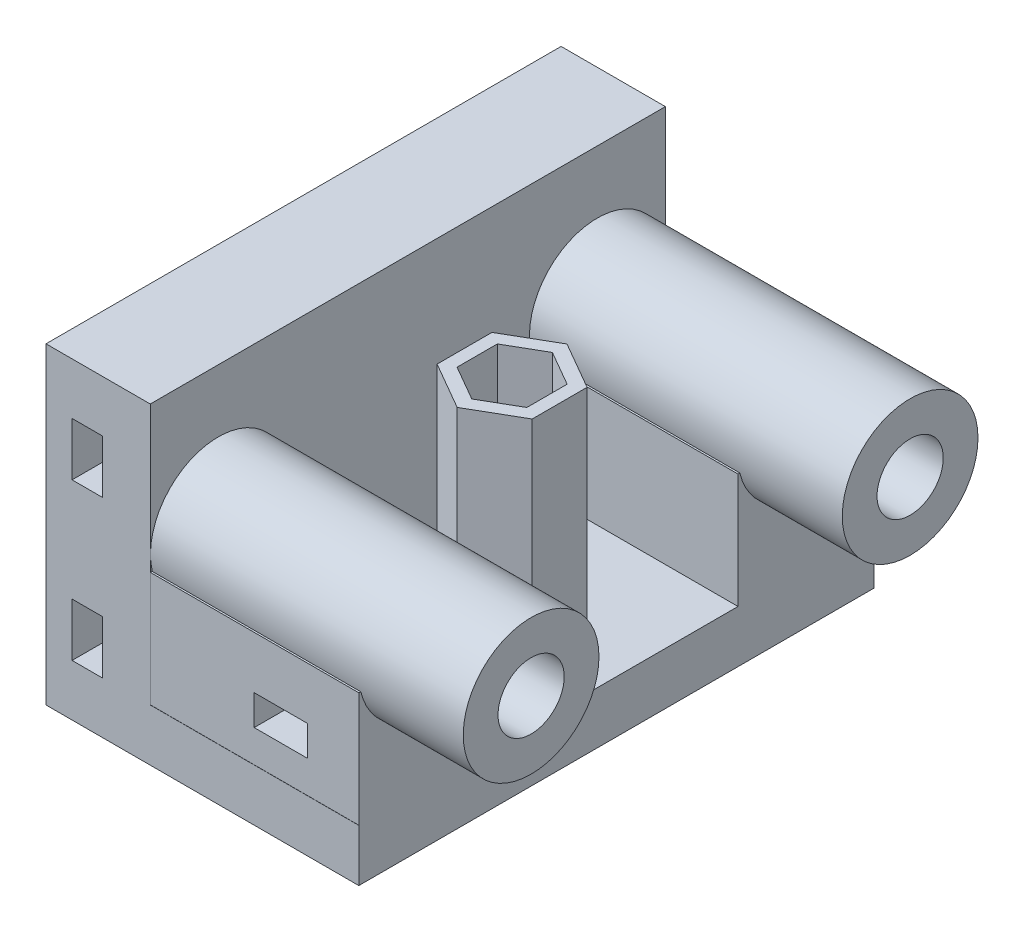
SolidWorks part; units mm, degrees
ref_plane "Front Plane" through (0, 0, 0) normal (0, 0, 1) x (1, 0, 0)
ref_plane "Top Plane" through (0, 0, 0) normal (0, 1, 0) x (1, 0, 0)
ref_plane "Right Plane" through (0, 0, 0) normal (1, 0, 0) x (0, 0, -1)
sketch "Sketch1" plane through (0, 0, 0) normal (1, 0, 0) x (0, 0, -1)
  line L1 (0, 0) -> (88.9, 0)
  line L2 (0, 0) -> (0, 76.2)
  line L3 (0, 76.2) -> (88.9, 76.2)
  line L4 (88.9, 0) -> (88.9, 76.2)
  dimension "D1" = 76.2
  dimension "D2" = 88.9
extrude "Boss-Extrude1" add sketch "Sketch1" along normal blind 25.4
sketch "Sketch2" plane through (0, 0, 0) normal (-1, 0, 0) x (0, 0, 1)
  line L0 (-88.9, 0) -> (-88.9, 76.2) construction
  line L1 (-82.55, 19.05) -> (-88.9, 19.05) construction
  line L2 (-82.55, 57.15) -> (-88.9, 57.15) construction
  line L3 (-44.45, 76.2) -> (-44.45, 0) construction
  line L4 (-88.9, 76.2) -> (0, 76.2) construction
  line L5 (0, 0) -> (-88.9, 0) construction
  circle A0 centre (-82.55, 57.15) radius 4.1021
  circle A1 centre (-82.55, 19.05) radius 4.1021
  circle A2 centre (-6.35, 19.05) radius 4.1021
  circle A3 centre (-6.35, 57.15) radius 4.1021
  dimension "D2" = 8.2042
  dimension "d1" = 19.05
  dimension "D3" = 6.35
  dimension "D4" = 38.1
  dimension "D5" = 76.2
extrude "Cut-Extrude1" cut sketch "Sketch2" against normal blind 19.05 contours A1 | A3 | A2 | A0 region at (0, 19.05, -82.55) region at (0, 19.05, -6.35) region at (0, 57.15, -6.35)
sketch "Sketch3" plane through (0, 0, 0) normal (0, 0, 1) x (1, 0, 0)
  line L0 (0, 61.2521) -> (0, 53.0479) construction
  line L1 (0, 57.15) -> (13.716, 57.15) construction
  line L2 (6.35, 63.627) -> (13.716, 63.627)
  line L3 (6.35, 63.627) -> (6.35, 50.673)
  line L4 (6.35, 50.673) -> (13.716, 50.673)
  line L5 (0, 38.1) -> (25.4, 38.1) construction
  line L6 (0, 76.2) -> (0, 0) construction
  line L7 (25.4, 76.2) -> (25.4, 0) construction
  line L8 (13.716, 12.573) -> (13.716, 25.527)
  line L9 (0, 61.2521) -> (0, 53.0479)
  line L11 (6.35, 25.527) -> (13.716, 25.527)
  line L12 (13.716, 63.627) -> (13.716, 50.673)
  line L13 (6.35, 12.573) -> (6.35, 25.527)
  line L14 (6.35, 12.573) -> (13.716, 12.573)
  dimension "D1" = 7.366
  dimension "D2" = 12.954
  dimension "D3" = 6.35
extrude "Cut-Extrude2" cut sketch "Sketch3" against normal blind 12.954 contours L12 L2 L3 L4 | L13 L14 L8 L11 region at (10.033, 57.15, 0) region at (10.033, 19.05, 0)
ref_plane "Plane1" through (0, 0, -44.45) normal (0, 0, 1) x (1, 0, 0)
mirror "Mirror1" about plane through (0, 0, -44.45) normal (0, 0, 1) of "Cut-Extrude2"
sketch "Sketch5" plane through (25.4, 0, 0) normal (1, 0, 0) x (0, 0, -1)
  line L0 (88.9, 0) -> (88.9, 76.2) construction
  line L1 (0, 0) -> (88.9, 0)
  line L2 (0, 0) -> (0, 12.7)
  line L3 (0, 12.7) -> (88.9, 12.7)
  line L4 (88.9, 0) -> (88.9, 12.7)
  dimension "D1" = 12.7
extrude "Boss-Extrude2" add sketch "Sketch5" along normal blind 50.8
sketch "Sketch6" plane through (25.4, 0, 0) normal (1, 0, 0) x (0, 0, -1)
  line L0 (-1.7145, 44.45) -> (90.6145, 44.45) construction
  line L3 (44.45, 76.2) -> (44.45, 12.7) construction
  line L4 (88.9, 76.2) -> (0, 76.2) construction
  line L5 (88.9, 12.7) -> (0, 12.7) construction
  line L6 (-1.7145, 44.45) -> (-1.7145, 60.9812) construction
  circle A0 centre (-1.7145, 44.45) radius 8.0645
  circle A1 centre (-1.7145, 44.45) radius 16.5312
  circle A2 centre (90.6145, 44.45) radius 8.0645
  circle A3 centre (90.6145, 44.45) radius 16.5312
  point P8 (44.45, 44.45)
  point P9 (44.45, 44.45)
  dimension "D2" = 16.129
  dimension "D3" = 8.4667
  dimension "D5" = 33.0623
  dimension "D4" = 16.5312
  dimension "V2" = 92.329
extrude "Boss-Extrude3" add sketch "Sketch6" along normal blind 76.2
sketch "Sketch7" plane through (0, 0, 0) normal (0, 0, 1) x (1, 0, 0)
  line L0 (25.4, 12.7) -> (25.4, 0)
  line L9 (25.4, 28.008) -> (25.4, 36.5699)
  line L10 (0, 76.2) -> (0, 0)
  line L11 (0, 0) -> (76.2, 0)
  line L12 (76.2, 0) -> (76.2, 12.7)
  line L13 (76.2, 12.7) -> (25.4, 12.7)
  line L14 (25.4, 12.7) -> (25.4, 28.008)
  line L15 (25.4, 28.008) -> (25.4, 36.5699)
  line L16 (25.4, 36.5699) -> (25.4, 52.3301)
  line L17 (25.4, 36.5699) -> (25.4, 52.3301)
  line L19 (25.4, 76.2) -> (0, 76.2)
  line L20 (0, 76.2) -> (0, 0)
  line L21 (0, 0) -> (76.2, 0)
  line L22 (76.2, 0) -> (76.2, 12.7)
  line L23 (76.2, 12.7) -> (25.4, 12.7)
  line L24 (25.4, 12.7) -> (25.4, 28.008)
  line L26 (25.4, 52.3301) -> (25.4, 60.892)
  line L27 (25.4, 52.3301) -> (25.4, 60.892)
  line L28 (25.4, 60.892) -> (25.4, 76.2)
  line L29 (25.4, 76.2) -> (0, 76.2)
  line L30 (25.4, 60.892) -> (25.4, 76.2)
  line M11 (13.716, 63.627) -> (13.716, 50.673)
  line M12 (13.716, 50.673) -> (6.35, 50.673)
  line M13 (6.35, 50.673) -> (6.35, 63.627)
  line M14 (6.35, 63.627) -> (13.716, 63.627)
  line M15 (0, 76.2) -> (0, 0)
  line M16 (0, 0) -> (76.2, 0)
  line M17 (76.2, 0) -> (76.2, 12.7)
  line M18 (76.2, 12.7) -> (25.4, 12.7)
  line M19 (25.4, 12.7) -> (25.4, 28.008)
  line M20 (25.4, 28.008) -> (25.4, 36.5699)
  line M21 (25.4, 36.5699) -> (25.4, 52.3301)
  line M22 (25.4, 52.3301) -> (25.4, 60.892)
  line M23 (25.4, 60.892) -> (25.4, 76.2)
  line M24 (25.4, 76.2) -> (0, 76.2)
  line M25 (6.35, 12.573) -> (6.35, 25.527)
  line M26 (6.35, 25.527) -> (13.716, 25.527)
  line M27 (13.716, 25.527) -> (13.716, 12.573)
  line M28 (13.716, 12.573) -> (6.35, 12.573)
  dimension "D1" = 0
extrude "Boss-Extrude4" add sketch "Sketch7" along normal blind 18.288 contours L0 M18 M16 M17 | L0 M19 M20 M21 M22 M23 M24 M15 M16 M28 M25 M26 M27 M14 M11 M12 M13 region at (50.8, 6.35, 0) region at (12.9917, 38.1, 0)
mirror "Mirror2" about plane through (0, 0, -44.45) normal (0, 0, 1) of "Boss-Extrude4"
sketch "Sketch8" plane through (0, 12.7, 0) normal (0, 1, 0) x (1, 0, 0)
  line L0 (101.6, 14.8167) -> (25.4, 14.8167) construction
  line L1 (25.4, -18.2457) -> (101.6, -18.2457) construction
  line L2 (101.6, 14.8167) -> (25.4, 14.8167)
  line L3 (25.4, -18.2457) -> (101.6, -18.2457)
  line L4 (25.4, 107.188) -> (25.4, -18.288)
  line L5 (25.4, -18.288) -> (76.2, -18.288)
  line L6 (76.2, -18.288) -> (76.2, 107.188)
  line L7 (76.2, 107.188) -> (25.4, 107.188)
  line L8 (25.4, 107.188) -> (25.4, -18.288)
  line L9 (25.4, -18.288) -> (76.2, -18.288)
  line L10 (76.2, -18.288) -> (76.2, 107.188)
  line L11 (76.2, 107.188) -> (25.4, 107.188)
  line L13 (25.4, 14.8167) -> (76.2, 14.8167)
  line L14 (25.4, 14.8167) -> (25.4, -18.2457)
  line L15 (25.4, -18.2457) -> (76.2, -18.2457)
  line L16 (76.2, 14.8167) -> (76.2, -18.2457)
  line M5 (25.4, 107.188) -> (25.4, -18.288)
  line M7 (76.2, -18.288) -> (76.2, 107.188)
  dimension "D1" = 0
extrude "Boss-Extrude5" add sketch "Sketch8" along normal blind 27.94 contours L3 L2 M5 M7 region at (50.8, 12.7, 1.7145)
sketch "Sketch11" plane through (101.6, 0, 0) normal (1, 0, 0) x (0, 0, -1)
  circle A0 centre (-1.7145, 44.45) radius 8.0645
  circle A1 centre (-1.7145, 44.45) radius 8.0645 construction
extrude "Cut-Extrude5" cut sketch "Sketch11" against normal blind 76.2
sketch "Sketch12" plane through (0, 0, 0) normal (0, -1, 0) x (1, 0, 0)
  line L0 (101.6, -6.35) -> (101.6, 9.779) construction
  line L1 (101.6, -6.35) -> (101.6, 9.779)
  line L2 (101.6, 1.7145) -> (0, 1.7145) construction
  line L3 (0, 18.288) -> (0, -107.188) construction
  line L4 (76.2, -14.3716) -> (76.2, 17.8006) construction
  line L5 (0, 18.288) -> (76.2, 18.288) construction
  line L6 (57.15, -2.3876) -> (57.15, 18.288) construction
  circle A0 centre (57.15, 1.7145) radius 4.1021
  dimension "D2" = 8.2042
  dimension "D3" = 20.6756
  dimension "D1" = 19.05
extrude "Cut-Extrude6" cut sketch "Sketch12" against normal up to next contours L2 A0 | A0 L2 region at (57.15, 0, 1.7145)
sketch "Sketch13" plane through (0, 0, 18.2457) normal (0, 0, 1) x (1, 0, 0)
  line L0 (53.0479, 0) -> (61.2521, 0) construction
  line L1 (53.0479, 0) -> (61.2521, 0)
  line L2 (57.15, 0) -> (57.15, 40.64) construction
  line L3 (25.4, 40.64) -> (76.2, 40.64) construction
  line L4 (76.2, 27.9188) -> (101.6, 27.9188) construction
  line L5 (76.2, 27.9188) -> (101.6, 27.9188)
  line L7 (50.673, 27.9188) -> (63.627, 27.9188)
  line L8 (50.673, 27.9188) -> (50.673, 20.5528)
  line L9 (50.673, 20.5528) -> (63.627, 20.5528)
  line L10 (63.627, 27.9188) -> (63.627, 20.5528)
  point P12 (57.15, 27.9188)
  dimension "D1" = 7.366
  dimension "D2" = 12.954
extrude "Cut-Extrude7" cut sketch "Sketch13" against normal blind 22.9616 contours L2 L9 L10 L7 | L9 L2 L7 L8 region at (53.9115, 24.2358, 18.2457) region at (60.3885, 24.2358, 18.2457)
mirror "Mirror3" about plane through (0, 0, -44.45) normal (0, 0, 1) of "Cut-Extrude7", "Cut-Extrude6", "Boss-Extrude5", "Cut-Extrude5"
sketch "Sketch14" plane through (0, 12.7, 0) normal (0, 1, 0) x (1, 0, 0)
  line L0 (25.4, 44.45) -> (76.2, 44.45) construction
  line L1 (25.4, 74.0833) -> (25.4, 14.8167) construction
  line L2 (76.2, 74.0833) -> (76.2, 14.8167) construction
  line L3 (50.8, 31.0767) -> (59.3, 39.5425) construction
  line L4 (42.3, 39.5425) -> (50.8, 34.635)
  line L5 (50.8, 34.635) -> (59.3, 39.5425)
  line L6 (59.3, 39.5425) -> (59.3, 49.3575)
  line L7 (59.3, 49.3575) -> (50.8, 54.265)
  line L8 (50.8, 54.265) -> (42.3, 49.3575)
  line L9 (42.3, 49.3575) -> (42.3, 39.5425)
  line L10 (50.8, 57.8233) -> (39.2184, 51.1366)
  line L11 (39.2184, 51.1366) -> (39.2184, 37.7634)
  line L12 (39.2184, 37.7634) -> (50.8, 31.0767)
  line L13 (50.8, 31.0767) -> (62.3816, 37.7634)
  line L14 (62.3816, 37.7634) -> (62.3816, 51.1366)
  line L15 (62.3816, 51.1366) -> (50.8, 57.8233)
  circle A0 centre (50.8, 44.45) radius 8.5 construction
  circle A1 centre (50.8, 44.45) radius 11.5816 construction
  circle A2 centre (50.8, 44.45) radius 5.25
  dimension "D2" = 10.5
  dimension "D1" = 17
  dimension "D3" = 8.4658
extrude "Boss-Extrude6" add sketch "Sketch14" along normal blind 50.8 contours L14 L15 L10 L11 L12 L13 L9 L8 L7 L6 L5 L4 region at (56.4139, 12.7, -54.1736)
extrude "Cut-Extrude8" cut sketch "Sketch14<3>" against normal up to next contours A2 region at (50.8, 12.7, -44.45)
sketch "Sketch14<3>" plane through (0, 12.7, 0) normal (0, 1, 0) x (1, 0, 0) same geometry as "Sketch14"
sketch "Sketch15" plane through (0, 0, 0) normal (0, -1, 0) x (1, 0, 0)
  line L1 (59.35, -39.5137) -> (50.8, -34.5773)
  line L2 (50.8, -34.5773) -> (42.25, -39.5137)
  line L3 (42.25, -39.5137) -> (42.25, -49.3863)
  line L4 (42.25, -49.3863) -> (50.8, -54.3227)
  line L5 (50.8, -54.3227) -> (59.35, -49.3863)
  line L6 (59.35, -49.3863) -> (59.35, -39.5137)
  circle A0 centre (50.8, -44.45) radius 8.55 construction
  dimension "D1" = 17.1
extrude "Cut-Extrude9" cut sketch "Sketch15" against normal blind 9
equation "\"d1\"= 0.75"
equation "\"d1@Sketch2\"  = \"d1\""
equation "\"V1\"= \"D2@Sketch6\""
equation "\"V2\"= \"V1\" + 3"
